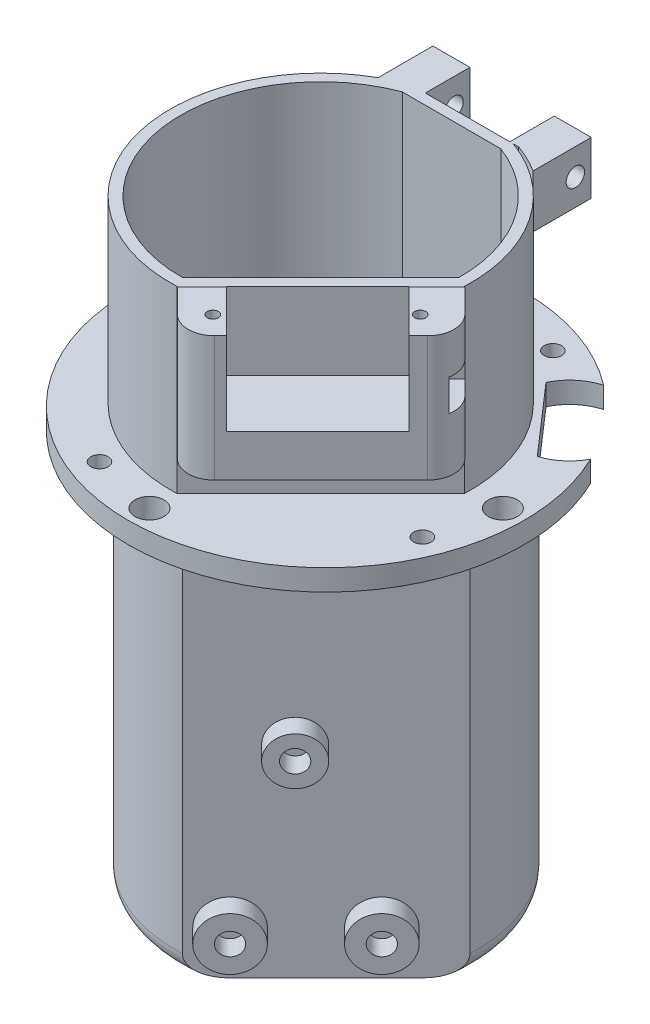
SolidWorks part; units mm, degrees
ref_plane "Front Plane" through (0, 0, 0) normal (0, 0, 1) x (1, 0, 0)
ref_plane "Top Plane" through (0, 0, 0) normal (0, 1, 0) x (1, 0, 0)
ref_plane "Right Plane" through (0, 0, 0) normal (1, 0, 0) x (0, 0, -1)
sketch "Sketch1" plane through (0, 0, 0) normal (0, 1, 0) x (1, 0, 0)
  circle A1 centre (0, 0) radius 37.5
  dimension "D1" = 75
extrude "Boss-Extrude1" add sketch "Sketch1" along normal blind 4
sketch "Sketch3" plane through (0, 4, 0) normal (0, 1, 0) x (1, 0, 0)
  line L3 (-4.5938, 27.6075) -> (3.8352, 27.6075) construction
  line L4 (27.4326, -1.2249) -> (0.1837, -28.4737)
  line L13 (25.4563, -0.3727) -> (-0.6684, -26.4974)
  line L14 (-10.7369, 26.8) -> (8.6548, 26.8)
  line L15 (26.0184, 0.1893) -> (-1.2305, -27.0595) construction
  line L16 (-10.3797, 24.8) -> (8.2976, 24.8)
  arc A4 (-10.3797, 24.8) -> (-0.6684, -26.4974) centre (-1.0411, 0) ccw
  arc A6 (-10.7369, 26.8) -> (0.1837, -28.4737) centre (-1.0411, 0) ccw
  arc A7 (27.4326, -1.2249) -> (8.6548, 26.8) centre (-1.0411, 0) ccw
  circle A8 centre (-1.0411, 0) radius 26.5 construction
  circle A9 centre (-1.0411, 0) radius 28.5 construction
  arc A10 (25.4563, -0.3727) -> (8.2976, 24.8) centre (-1.0411, 0) ccw
  point P1 (26.5, 0)
  point P2 (6.527, 25.6845)
  point P3 (0, 0)
  point P5 (27.2547, 8.3326)
  point P6 (8.0312, 25.2546)
  point P17 (25.3421, 7.7479)
  point P22 (28.5, 0)
  dimension "D1" = 53
  dimension "D4" = 2
  dimension "D5" = 26.8
  dimension "D6" = 2
  dimension "D2" = 2
extrude "Boss-Extrude2" add sketch "Sketch3" along normal blind 34
sketch "Sketch5" plane through (0, 4, 0) normal (0, 1, 0) x (1, 0, 0)
  line L0 (0, 0) -> (-12.1624, 0) construction
  line L1 (0, 0) -> (-12.362, -30.5971) construction
  circle A0 centre (-33.4949, 0.0001) radius 2.75
  circle A1 centre (-0.0001, 33.4948) radius 2.75
  circle A2 centre (33.4945, 0) radius 2.75
  circle A3 centre (-0.0003, -33.4947) radius 2.75
  circle A4 centre (-12.362, -30.5971) radius 1.65
  circle A5 centre (-30.5971, 12.362) radius 1.65
  circle A6 centre (12.362, 30.5971) radius 1.65
  circle A7 centre (30.5971, -12.362) radius 1.65
  point P12 (-0.0002, 0.0001)
  point P24 (0, 0)
  dimension "D1" = 5.5
  dimension "D5" = 3.3
  dimension "D3" = 33
  dimension "D4" = 68
  dimension "D2" = 4
  dimension "D6" = 4
extrude "Cut-Extrude2" cut sketch "Sketch5" against normal blind 10
sketch "Sketch6" plane through (0, 4, 0) normal (0, 1, 0) x (1, 0, 0)
  line L0 (18.5052, 32.5947) -> (37.1734, 4.7492) construction
sketch "Sketch8" plane through (0, 4, 0) normal (0, 1, 0) x (1, 0, 0)
  line L0 (35.6942, 8.1139) -> (20.6034, 30.6234)
  line L1 (20.6034, 30.6234) -> (21.1307, 30.977)
  line L2 (35.6942, 8.1139) -> (36.4519, 8.6219)
  arc A1 (36.4519, 8.6219) -> (21.1307, 30.977) centre (-0.6007, -0.3445) ccw
sketch "Sketch15" plane through (0, 0, 0) normal (0, -1, 0) x (1, 0, 0)
  line L0 (28.4737, 1.2249) -> (1.2248, 28.4737)
  line L1 (0.1837, 28.4737) -> (27.4326, 1.2249) construction
  line L2 (9.6959, -26.8) -> (-9.6959, -26.8)
  arc A2 (1.2248, 28.4737) -> (-9.6959, -26.8) centre (0, 0) ccw
  arc A3 (9.6959, -26.8) -> (28.4737, 1.2249) centre (0, 0) ccw
extrude "Boss-Extrude6" add sketch "Sketch15" along normal blind 75 separate body
shell "Shell1" thickness 2 removed face at (2.6415, 0, -5.5727)
sketch "Sketch16" plane through (0, 4, 0) normal (0, 1, 0) x (1, 0, 0)
  line L0 (0.3726, -26.4974) -> (26.4974, -0.3727) construction
  line L1 (0.3726, -26.4974) -> (26.4974, -0.3727)
  arc A0 (26.4974, -0.3727) -> (0.3726, -26.4974) centre (0, 0) ccw
extrude "Cut-Extrude3" cut sketch "Sketch16" against normal blind 10
fillet "Fillet1" radius 4 1 edges at (-27.9595, -75, 5.5241)
sketch "Sketch18" plane through (0, 38, 0) normal (0, 1, 0) x (1, 0, 0)
  line L0 (0, 0) -> (0, 17.814) construction
  line L1 (0, 0) -> (18.6321, 0) construction
  line L2 (15, 24.2332) -> (15, 35.2332)
  line L3 (15, 35.2332) -> (8, 35.2332)
  line L4 (8, 35.2332) -> (8, 26.8)
  line L12 (-8, 35.2332) -> (-8, 26.8)
  line L13 (-15, 35.2332) -> (-8, 35.2332)
  line L14 (-15, 24.2332) -> (-15, 35.2332)
  line L15 (-9.6959, 26.8) -> (-8, 26.8)
  line L16 (8.6548, 26.8) -> (-10.7369, 26.8) construction
  line L17 (9.6959, 26.8) -> (8, 26.8)
  circle A0 centre (-1.0411, 0) radius 28.5 construction
  arc A4 (-15, 24.2332) -> (-9.6959, 26.8) centre (0, 0) cw
  arc A6 (15, 24.2332) -> (9.6959, 26.8) centre (0, 0) ccw
  dimension "D1" = 11
  dimension "D2" = 15
  dimension "D3" = 7
extrude "Boss-Extrude9" add sketch "Sketch18" against normal blind 10
sketch "Sketch21" plane through (15, 0, 0) normal (1, 0, 0) x (0, 0, -1)
  circle A0 centre (32.2332, 33) radius 1.75
extrude "Cut-Extrude5" cut sketch "Sketch21" against normal blind 40
ref_plane "Plane1" through (-20.1525, 0, -20.1526) normal (-0.7071, 0, -0.7071) x (-0.7071, 0, 0.7071)
sketch "Sketch25" plane through (0, 38, 0) normal (0, 1, 0) x (1, 0, 0)
  line L0 (-25.1825, 8.2516) -> (15.2441, -21.6764)
  arc A0 (-25.1825, 8.2516) -> (15.2441, -21.6764) centre (0, 0) ccw
sketch "Sketch27" plane through (14.3287, 0, 14.3287) normal (0.7071, 0, 0.7071) x (0.7071, 0, -0.7071)
  line L0 (-20.6787, 21.6433) -> (17.857, 21.6433) construction
  line L3 (-13.3566, 23.3821) -> (-13.3566, 39.0821)
  line L5 (-13.3566, 39.0821) -> (-19.9426, 39.0821)
  line L6 (0, 0) -> (0, 35.7163) construction
  line L9 (-19.9426, 15.3821) -> (-19.9426, 39.0821)
  line L10 (-13.3566, 23.3821) -> (11.1231, 23.3821)
  line L12 (-19.9426, 15.3821) -> (18.5931, 15.3821)
  line L13 (18.5931, 15.3821) -> (18.5931, 39.0821)
  line L14 (19.2678, 0) -> (-19.2678, 0) construction
  line L15 (18.5931, 39.0821) -> (11.1231, 39.0821)
  line L16 (11.1231, 39.0821) -> (11.1231, 23.3821)
extrude "Boss-Extrude13" add sketch "Sketch27" along normal blind 13
fillet "Fillet2" radius 5 2 edges at (9.4195, 27.2321, 37.6226) (36.6684, 27.2321, 10.3738)
sketch "Sketch28" plane through (0, 39.0821, 0) normal (0, 1, 0) x (1, 0, 0)
  circle A0 centre (9.3165, -30.7961) radius 1.05
  circle A1 centre (28.9741, -11.1385) radius 1.05
  dimension "D1" = 2.1
  dimension "D2" = 2.1
extrude "Cut-Extrude11" cut sketch "Sketch28" against normal blind 6
sketch "Sketch29" plane through (0, -73, 0) normal (0, 1, 0) x (1, 0, 0)
  circle A0 centre (0, 0) radius 3.25
  dimension "D1" = 6.5
extrude "Cut-Extrude12" cut sketch "Sketch29" against normal blind 6
sketch "Sketch31" plane through (13.1474, 0, -13.1473) normal (0.7071, 0, -0.7071) x (-0.7071, 0, -0.7071)
  line L1 (-32.3639, 25.6615) -> (-24.3639, 25.6615)
  line L2 (-32.3639, 25.6615) -> (-32.3639, 31.6615)
  line L3 (-32.3639, 31.6615) -> (-24.3639, 31.6615)
  line L4 (-24.3639, 25.6615) -> (-24.3639, 31.6615)
  line L5 (-32.3639, 25.6615) -> (-24.3639, 31.6615) construction
  line L6 (-32.3639, 31.6615) -> (-24.3639, 25.6615) construction
  point P0 (-28.3639, 28.6615)
  dimension "D1" = 6
  dimension "D2" = 8
extrude "Cut-Extrude13" cut sketch "Sketch31" against normal blind 10
sketch "Sketch32" plane through (0, 38, 0) normal (0, 1, 0) x (1, 0, 0)
  line L0 (-9.3386, 24.8) -> (9.3386, 24.8) construction
  line L2 (-9.3386, 24.8) -> (9.3386, 24.8)
  arc A0 (26.4974, -0.3727) -> (0.3726, -26.4974) centre (0, 0) ccw construction
  arc A1 (9.3386, 24.8) -> (-9.3386, 24.8) centre (0, 0) ccw
extrude "Boss-Extrude14" add sketch "Sketch32" along normal blind 10 from vertex starting at point (9.3386, 0, -24.8)
sketch "Sketch33" plane through (14.8492, 0, 14.8493) normal (0.7071, 0, 0.7071) x (0.7071, 0, -0.7071)
  circle A0 centre (-12.8786, -66.6999) radius 5
  circle A1 centre (7.4614, -66.6999) radius 5
  circle A2 centre (-4.1537, -36.6999) radius 4.5
  dimension "D1" = 10
  dimension "D2" = 10
  dimension "D3" = 9
extrude "Boss-Extrude15" add sketch "Sketch33" along normal up to surface (3.86 mm away)
sketch "Sketch34" plane through (17.5786, 0, 17.5787) normal (0.7071, 0, 0.7071) x (0.7071, 0, -0.7071)
  circle A0 centre (-4.1537, -36.6999) radius 2.1
  circle A1 centre (7.4614, -66.6999) radius 2.1
  circle A2 centre (-12.8786, -66.6999) radius 2.1
  dimension "D1" = 4.2
  dimension "D2" = 4.2
  dimension "D3" = 4.2
extrude "Cut-Extrude14" cut sketch "Sketch34" against normal blind 4.2
sketch "Sketch35" plane through (0, 4, 0) normal (0, 1, 0) x (1, 0, 0)
  line L0 (16.9305, 24.732) -> (28.2571, 11.758)
  arc A0 (28.2571, 11.758) -> (16.9305, 24.732) centre (25.4201, 20.7124) ccw
extrude "Cut-Extrude15" cut sketch "Sketch35" against normal blind 6
sketch "Sketch36" plane through (0, 39.0821, 0) normal (0, 1, 0) x (1, 0, 0)
  line L0 (27.476, -1.1814) -> (28.6465, -2.3519)
  line L1 (28.6465, -2.3519) -> (1.3976, -29.6007)
  line L3 (1.3976, -29.6007) -> (0.2271, -28.4302)
  line L4 (0.2271, -28.4302) -> (27.476, -1.1814)
extrude "Cut-Extrude16" cut sketch "Sketch36" against normal up to surface (1.0821 mm away) up to face at (3.7925, 38, -13.738)
